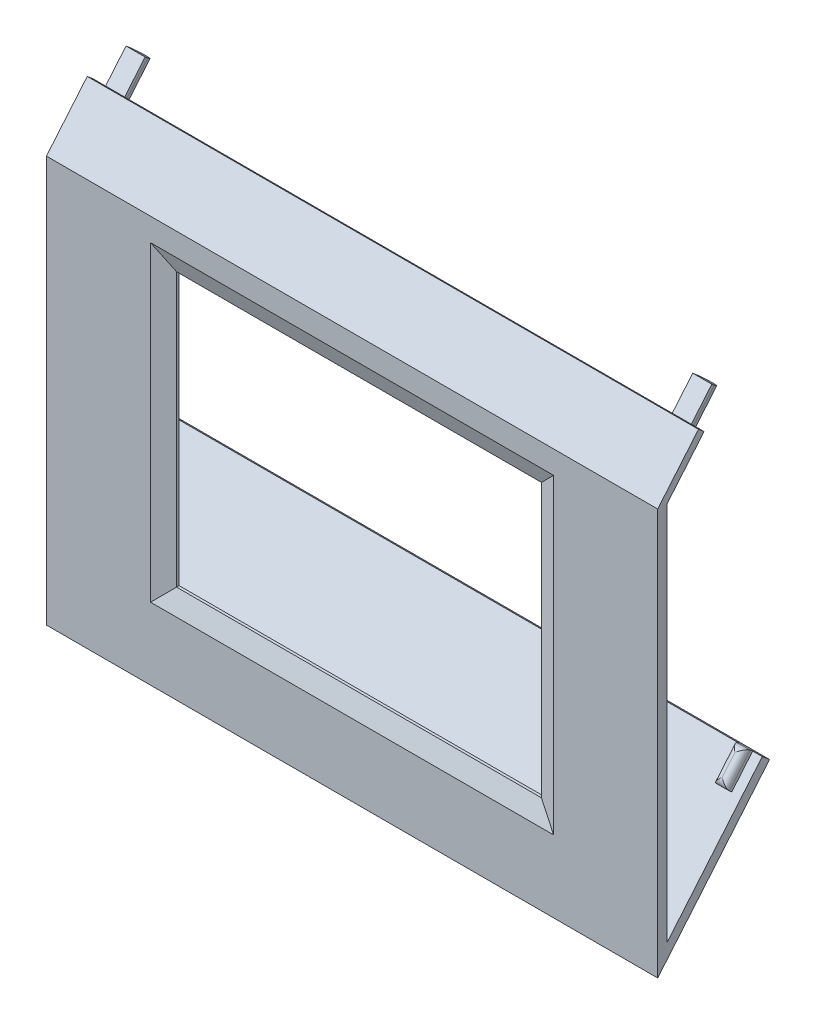
SolidWorks part; units mm, degrees
ref_plane "Спереди" through (0, 0, 0) normal (0, 0, 1) x (1, 0, 0)
ref_plane "Сверху" through (0, 0, 0) normal (0, 1, 0) x (1, 0, 0)
ref_plane "Справа" through (0, 0, 0) normal (1, 0, 0) x (0, 0, -1)
sketch "Эскиз1" plane through (0, 0, 0) normal (0, 0, 1) x (1, 0, 0)
  line L0 (46, -35) -> (-46, -35)
  line L1 (30, -22.5) -> (-30, -22.5)
  line L2 (30, -22.5) -> (30, 22.5)
  line L3 (30, 22.5) -> (-30, 22.5)
  line L4 (-30, -22.5) -> (-30, 22.5)
  line L7 (46, -25) -> (-46, -25) construction
  line L8 (46, -25) -> (46, 25) construction
  line L9 (46, 25) -> (-46, 25) construction
  line L10 (-46, -25) -> (-46, 25) construction
  line L13 (46, 27) -> (-46, 27)
  line L14 (-48, -25) -> (-48, 25)
  line L15 (48, -25) -> (48, 25)
  line L16 (-46, -35) -> (-48, -35)
  line L17 (-48, -35) -> (-48, -25)
  line L18 (-46, 27) -> (-48, 27)
  line L19 (-48, 27) -> (-48, 25)
  line L20 (46, -35) -> (48, -35)
  line L21 (48, -35) -> (48, -25)
  line L22 (46, 27) -> (48, 27)
  line L23 (48, 27) -> (48, 25)
  point P0 (0, 0)
  point P6 (0, 0)
  dimension "D1" = 45
  dimension "D2" = 60
  dimension "D3" = 50
  dimension "D4" = 92
  dimension "D5" = 10
  dimension "D6" = 2
  dimension "D7" = 2
  dimension "D8" = 2
extrude "Бобышка-Вытянуть1" add sketch "Эскиз1" along normal blind 1.5
sketch "Эскиз2" plane through (48, 0, 0) normal (1, 0, 0) x (0, 0, -1)
  line L0 (0, -35) -> (16.0697, -15.8489)
  line L1 (-1.1491, -34.0358) -> (14.9206, -14.8847)
  line L2 (0, 27) -> (9.6681, 38.522)
  line L3 (-1.5, 27) -> (8.7879, 39.2606)
  line L4 (8.7879, 39.2606) -> (9.6681, 38.522)
  line L5 (-1.5, 27) -> (0, 27)
  line L6 (-1.1491, -34.0358) -> (0, -35)
  line L7 (14.9206, -14.8847) -> (16.0697, -15.8489)
  line L8 (0, 27) -> (-1.5, 27)
  line M3 (0, -35) -> (0, 27)
  line M4 (0, 27) -> (-1.5, 27)
  dimension "D1" = 25
  dimension "D2" = 1.5
extrude "Бобышка-Вытянуть2" add sketch "Эскиз2" against normal blind 96 contours L4 L3 L2 M4 | L7 L1 L0 M3 region at (48, -24.6102, -7.7511) region at (48, 32.9476, -4.2328)
sketch "Эскиз4" plane through (0, 0, 1.5) normal (0, 0, 1) x (1, 0, 0)
  line L0 (30, -22.5) -> (30, 22.5) construction
  line L1 (-30, 22.5) -> (30, 22.5)
  line L2 (-30, 22.5) -> (-30, 20.4)
  line L3 (-30, 20.4) -> (30, 20.4)
  line L4 (30, 22.5) -> (30, 20.4)
  line L6 (-30, -22.5) -> (30, -22.5) construction
  dimension "D1" = 42.9
extrude "Бобышка-Вытянуть3" add sketch "Эскиз4" against normal blind 1.5
sketch "Эскиз6" plane through (0, 0, 1.5) normal (0, 0, 1) x (1, 0, 0)
  line L0 (-30, 20.4) -> (30, 20.4) construction
  line L2 (28.65, -20.7) -> (28.65, 20.4)
  line L3 (28.65, 20.4) -> (-28.65, 20.4)
  line L4 (-28.65, -20.7) -> (-28.65, 20.4)
  line L7 (-28.65, 20.4) -> (-28.65, -22.5)
  line L8 (-30, -22.5) -> (30, -22.5) construction
  line L9 (-28.65, -22.5) -> (28.65, -22.5)
  line L10 (28.65, -22.5) -> (28.65, 20.4)
  line L11 (30, 20.4) -> (30, -22.5)
  line L12 (30, -22.5) -> (-30, -22.5)
  line L13 (-30, -22.5) -> (-30, 20.4)
  line L14 (-30, 20.4) -> (-28.65, 20.4)
  point P0 (0, 0)
  line M2 (-30, -22.5) -> (-30, 20.4)
  line M3 (-30, 20.4) -> (30, 20.4)
  line M4 (30, 20.4) -> (30, -22.5)
  line M5 (30, -22.5) -> (-30, -22.5)
  dimension "D1" = 57.3
extrude "Бобышка-Вытянуть4" add sketch "Эскиз6" against normal blind 1.5 contours L7 L4 M3 M2 M5 | L10 L2 M5 M4 M3 region at (29.325, -1.05, 1.5) region at (-29.325, -1.05, 1.5)
sketch "Эскиз8" plane through (48, 0, 0) normal (1, 0, 0) x (0, 0, -1)
  line L0 (0, 27) -> (9.6681, 38.522) construction
  line L1 (5.7851, 33.8944) -> (4.9049, 34.633)
  line L2 (-1.5, 27) -> (8.7879, 39.2606) construction
  line L3 (4.9049, 34.633) -> (8.7879, 39.2606)
  line L4 (8.7879, 39.2606) -> (9.6681, 38.522)
  line L5 (9.6681, 38.522) -> (5.7851, 33.8944)
  point P0 (5.7851, 33.8944)
  dimension "D1" = 9
extrude "Вырез-Вытянуть2" cut sketch "Эскиз8" against normal blind 100
sketch "Эскиз9" plane through (48, 0, 0) normal (1, 0, 0) x (0, 0, -1)
  line L0 (-1.5, -35) -> (-1.5, -36.7876)
  line L1 (0, -35) -> (-1.5, -35)
  line L3 (0, -35) -> (-1.5, -36.7876)
extrude "Бобышка-Вытянуть5" add sketch "Эскиз9" against normal blind 96 contours L0 L3 L1
sketch "Эскиз10" plane through (0, 0, 1.5) normal (0, 0, 1) x (1, 0, 0)
  line L1 (-28.65, 20.4) -> (28.65, 20.4)
  line L2 (-28.65, 20.4) -> (-28.65, -22.5)
  line L3 (-28.65, -22.5) -> (28.65, -22.5)
  line L4 (28.65, 20.4) -> (28.65, -22.5)
sketch "Эскиз12" plane through (0, 11.1557, 13.2949) normal (0, -0.6428, -0.766) x (-1, 0, 0)
  line L0 (-48, 20.6832) -> (48, 20.6832) construction
  line L1 (48, 20.6832) -> (48, -25.0239) construction
  line L2 (48, 29.6832) -> (-48, 29.6832) construction
  line L3 (46, 20.6832) -> (43, 20.6832)
  line L4 (46, 20.6832) -> (46, 34.6832)
  line L5 (46, 34.6832) -> (43, 34.6832)
  line L6 (43, 20.6832) -> (43, 34.6832)
  line L7 (0, 29.6832) -> (0, 25.6437) construction
  line L8 (-43, 20.6832) -> (-43, 34.6832)
  line L9 (-46, 34.6832) -> (-43, 34.6832)
  line L10 (-46, 20.6832) -> (-46, 34.6832)
  line L11 (-46, 20.6832) -> (-43, 20.6832)
  point P0 (46, 20.6832)
  point P9 (43, 29.6832)
  point P19 (-43, 29.6832)
  dimension "D1" = 2
  dimension "D2" = 3
  dimension "D3" = 14
extrude "Бобышка-Вытянуть6" add sketch "Эскиз12" along normal blind 2
fillet "Скругление1" radius 1.5 6 edges at (-43, 31.0767, -6.0316) (-46, 31.0767, -6.0316) (-44.5, 25.7144, -1.5321) (46, 31.0767, -6.0316) (43, 31.0767, -6.0316) (44.5, 25.7144, -1.5321)
sketch "Эскиз13" plane through (0, -13.497, -16.0851) normal (0, 0.6428, 0.766) x (1, 0, 0)
  line L0 (-48, -1.8116) -> (48, -1.8116) construction
  line L1 (-46.5, -1.8116) -> (-44.5, -1.8116)
  line L2 (-46.5, -1.8116) -> (-46.5, -6.9146)
  line L3 (-46.5, -6.9146) -> (-44.5, -6.9146)
  line L4 (-44.5, -1.8116) -> (-44.5, -6.9146)
  line L5 (-48, -25.0239) -> (-48, -1.8116) construction
  line L6 (0, 48.9963) -> (0, 0) construction
  line L7 (44.5, -1.8116) -> (44.5, -6.9146)
  line L8 (46.5, -6.9146) -> (44.5, -6.9146)
  line L9 (46.5, -1.8116) -> (46.5, -6.9146)
  line L10 (46.5, -1.8116) -> (44.5, -1.8116)
  dimension "D1" = 1.5
  dimension "D2" = 2
extrude "Бобышка-Вытянуть7" add sketch "Эскиз13" along normal blind 1.5
fillet "Скругление3" radius 1 8 edges at (-45.5, -13.9205, -13.7716) (-45.5, -17.8297, -10.4914) (-44.5, -15.8751, -12.1315) (-46.5, -15.8751, -12.1315) (45.5, -13.9205, -13.7716) (45.5, -17.8297, -10.4914) (44.5, -15.8751, -12.1315) (46.5, -15.8751, -12.1315)
chamfer "Фаска3" distance 3 angle 20 4 edges at (28.65, -1.05, 1.5) (0, -22.5, 1.5) (-28.65, -1.05, 1.5) (0, 20.4, 1.5) first distance on face at (0, -1.05, 1.5)
